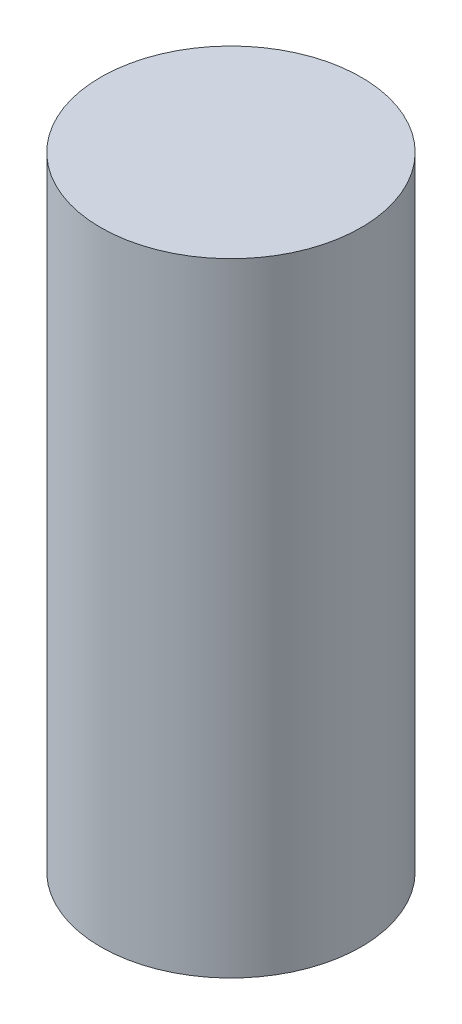
SolidWorks part; units mm, degrees
ref_plane "Front Plane" through (0, 0, 0) normal (0, 0, 1) x (1, 0, 0)
ref_plane "Top Plane" through (0, 0, 0) normal (0, 1, 0) x (1, 0, 0)
ref_plane "Right Plane" through (0, 0, 0) normal (1, 0, 0) x (0, 0, -1)
sketch "Sketch1" plane through (0, 0, 0) normal (0, 1, 0) x (1, 0, 0)
  circle A0 centre (0, 0) radius 3
  dimension "D1" = 6
extrude "Boss-Extrude1" add sketch "Sketch1" along normal blind 14.346
equation "\"bearing_21_OD\"= 21mm"
equation "\"pin_cirlce_diameter\"= 75mm"
equation "\"pin_diam\"= 6mm"
equation "\"gear_thickness\"= 4mm"
equation "\"ball_bearing_diam\"= 3.214mm"
equation "\"bearing_21_outer_clearance\"= 0.127mm'change this"
equation "\"bearing_15_OD\"= 15mm"
equation "\"bearing_15_outer_clearance\"= 0mm'change this"
equation "\"thrust_bearing_thickness\"= 5mm'measure this irl and change"
equation "\"D1@Boss-Extrude1\"=\"ballBearDiam\"*1.50+2*\"sheetThickness\""
equation "\"largeBearOD\"= 21mm"
equation "\"largeBearID\" = 15mm"
equation "\"largeBearOTight\"= 0.127mm'calibrate - hold onto gears"
equation "\"largeBearITight\"= 0mm'calibrate - hold onto eccentric nut"
equation "\"largeBearFlangeDiam\" = 22.5mm"
equation "\"largeBearFlangeWidth\" = 0.8mm"
equation "\"smallBearOD\"= 15mm"
equation "\"smallBearOTight\"= 0mm'calibrate - hold onto bottom of gearbox"
equation "\"smallBearOLoose\"= 0mm'calibrate - able to take off topHat"
equation "\"smallBearID\" = 10mm"
equation "\"smallBearITight\" = 0mm'hold onto "
equation "\"pinCircleDiam\"= 75mm"
equation "\"pinDiam\"= 6mm"
equation "\"sheetThickness\"= 0.1875in"
equation "\"ballBearDiam\"= 3.214mm"
equation "\"thrustBearingThickness\"= 5mm'measure this irl and change"
equation "\"thrustBearingID\"= 0mm'measure this irl and change"
equation "\"thrustBearingOD\"= 0mm'measure this irl and change"
equation "\"eccentricity\" = 1mm"
equation "\"D1@Sketch1\"=\"pinDiam\""
